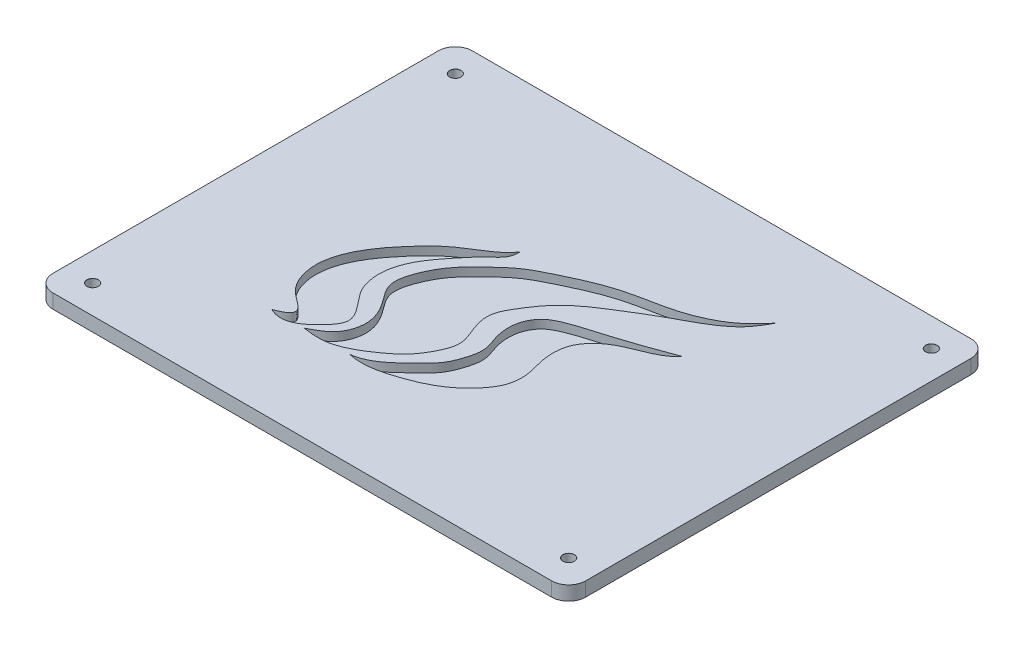
SolidWorks part; units mm, degrees
ref_plane "Plano frontal" through (0, 0, 0) normal (0, 0, 1) x (1, 0, 0)
ref_plane "Plano superior" through (0, 0, 0) normal (0, 1, 0) x (1, 0, 0)
ref_plane "Plano direito" through (0, 0, 0) normal (1, 0, 0) x (0, 0, -1)
ref_plane "Plano1" through (0, -5, 0) normal (0, -1, 0) x (1, 0, 0)
sketch "Esboço1" plane through (0, -5, 0) normal (0, -1, 0) x (1, 0, 0)
  line L0 (0, -148) -> (188, -148)
  line L1 (188, -148) -> (188, 0)
  line L2 (188, 0) -> (0, 0)
  line L3 (0, 0) -> (0, -148)
extrude "Ressalto-extrusão1" add sketch "Esboço1" against normal blind 5
sketch "Esboço2" plane through (0, -5, 0) normal (0, -1, 0) x (1, 0, 0)
  line L0 (5, -5) -> (183, -5)
  line L1 (183, -5) -> (183, -143)
  line L2 (183, -143) -> (5, -143)
  line L3 (5, -143) -> (5, -5)
extrude "Ressalto-extrusão2" add sketch "Esboço2" along normal blind 5
sketch "Esboço3" plane through (0, 0, 0) normal (0, 1, 0) x (-1, 0, 0)
  spline S0 degree 3 poles (-75.8513, -94.906) (-72.8535, -90.4619) (-63.519, -86.5735) (-53.3882, -76.0624) (-46.2023, -66.6508) (-42.9339, -55.6874) (-44.8426, -47.1017) (-50.6606, -40.2907) (-58.6418, -36.77) (-49.6316, -33.5768) knots 0 0 0 0 0.221731 0.361071 0.538534 0.656522 0.776882 0.841137 1 1 1 1
  spline S1 degree 3 poles (-49.6316, -33.5768) (-55.1932, -30.8638) (-61.3839, -35.1823) (-67.8569, -43.2627) (-64.0282, -49.8709) (-58.1961, -55.5638) (-57.0305, -66.1333) (-61.21, -75.4924) (-66.5475, -81.8637) (-71.7761, -88.296) (-76.1964, -90.9559) (-75.8513, -94.906) knots 0 0 0 0 0.190021 0.27318 0.335509 0.44453 0.578502 0.692991 0.817664 0.88529 1 1 1 1
extrude "Corte-extrusão1" cut sketch "Esboço3" against normal blind 3
sketch "Esboço4" plane through (0, 0, 0) normal (0, 1, 0) x (-1, 0, 0)
  spline S0 degree 3 poles (-136.7297, -91.7327) (-130.548, -89.419) (-121.9958, -86.2855) (-111.4177, -83.31) (-105.4901, -81.3156) (-100.2096, -78.9101) (-97.1664, -73.8232) (-96.8303, -68.8944) (-97.7553, -63.9422) (-99.9783, -59.2599) (-98.6794, -53.2404) (-96.4396, -47.1702) (-88.7973, -40.1703) (-83.295, -34.4435) (-77.2093, -33.5768) knots 0 0 0 0 0.208187 0.287593 0.345987 0.406774 0.465273 0.52264 0.558971 0.624214 0.679619 0.74702 0.825667 1 1 1 1
  spline S1 degree 3 poles (-77.2093, -33.5768) (-82.5851, -32.319) (-91.3527, -34.4282) (-101.3989, -38.5316) (-107.5302, -43.0726) (-111.3527, -47.2007) (-114.2478, -51.9233) (-114.9383, -56.8005) (-114.1515, -61.4169) (-112.8663, -65.5978) (-112.4174, -70.2105) (-113.0072, -74.7648) (-115.8896, -79.4687) (-123.6948, -85.6994) (-132.4436, -86.9091) (-136.7297, -91.7327) knots 0 0 0 0 0.166387 0.277066 0.33674 0.403034 0.451941 0.507331 0.552146 0.597486 0.643567 0.696221 0.737301 0.812803 1 1 1 1
extrude "Corte-extrusão2" cut sketch "Esboço4" against normal blind 3
ref_plane "Plano2" through (0, -9, 0) normal (0, 1, 0) x (1, 0, 0)
sketch "Esboço5" plane through (0, -9, 0) normal (0, 1, 0) x (1, 0, 0)
  spline S0 degree 3 poles (142.7977, 118.3188) (141.5574, 116.1036) (139.133, 111.7737) (133.2828, 107.1268) (127.0167, 103.5038) (120.5507, 100.1522) (114.3105, 96.3948) (108.1243, 92.5597) (102.0741, 88.4936) (96.7829, 83.3592) (92.8219, 77.3269) (88.9832, 70.7249) (90.8449, 63.3932) (94.2742, 56.7643) (91.4301, 49.5234) (87.454, 43.4921) (81.5905, 38.9932) (75.492, 35.0818) (68.3981, 32.6003) (63.5148, 33.2504) (61.0626, 33.5768) knots 0 0 0 0 0.057637 0.112657 0.168143 0.223818 0.279375 0.335006 0.390602 0.4463 0.501841 0.557867 0.611847 0.66681 0.721725 0.777322 0.832941 0.888514 0.944017 1 1 1 1
  spline S1 degree 3 poles (61.0626, 33.5768) (63.7068, 34.9359) (68.9279, 37.6195) (71.5706, 46.8653) (67.9201, 54.8174) (61.573, 61.5577) (64.0816, 70.7817) (68.2137, 78.2638) (74.4803, 84.3186) (80.7865, 90.2357) (88.5732, 94.0884) (96.3256, 97.7809) (104.4036, 100.8664) (112.8289, 102.6904) (121.3013, 104.2953) (129.403, 107.2855) (136.9905, 111.7221) (140.847, 116.1029) (142.7977, 118.3188) knots 0 0 0 0 0.062549 0.123506 0.186161 0.247751 0.310956 0.373508 0.436067 0.498651 0.561042 0.623646 0.68612 0.748656 0.811154 0.873632 0.93608 1 1 1 1
extrude "Corte-extrusão3" cut sketch "Esboço5" against normal blind 3 from surface starting at face at (106.9695, 0, -62.6548)
hole_wizard "Furo de diâmetro Ø4.0 (4)1" positions "Esboço7" profile "Esboço6" hole size "Ø4.0" standard "Ansi Metric"
sketch "Esboço7" plane through (0, 0, 0) normal (0, 1, 0) x (1, 0, 0)
  point P0 (178, 138)
  point P1 (178, 10)
  point P2 (10, 10)
  point P3 (10, 138)
sketch "Esboço6" plane through (178, 0, -138) normal (1, 0, 0) x (0, 0, 1)
  line L0 (0, 0) -> (0, 10)
  line L1 (0, 10) -> (2, 10)
  line L2 (2, 10) -> (2, 0)
  line L5 (2, 0) -> (0, 0)
  line L11 (0, -6.35) -> (0, 107.95) construction
  dimension "Thru Hole Dia." = 4
  dimension "Thru Hole Depth" = 10
chamfer "Chanfro1" distance 0.025 angle 45 4 edges at (10, 0, -136) (10, 0, -8) (178, 0, -8) (178, 0, -136)
fillet "Filete1" radius 6 8 edges at (0, -2.5, -148) (188, -2.5, 0) (188, -2.5, -148) (5, -7.5, -143) (0, -2.5, 0) (183, -7.5, -5) (5, -7.5, -5) (183, -7.5, -143) tangent propagation no
